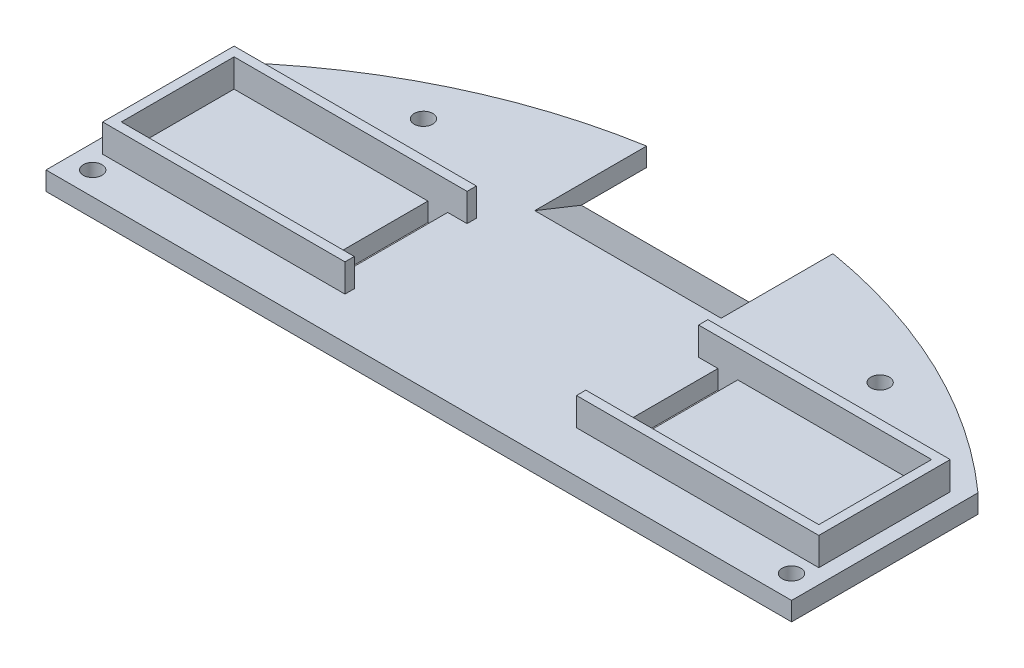
SolidWorks part; units mm, degrees
ref_plane "Front Plane" through (0, 0, 0) normal (0, 0, 1) x (1, 0, 0)
ref_plane "Top Plane" through (0, 0, 0) normal (0, 1, 0) x (1, 0, 0)
ref_plane "Right Plane" through (0, 0, 0) normal (1, 0, 0) x (0, 0, -1)
sketch "Sketch2" plane through (0, 0, 0) normal (0, 1, 0) x (1, 0, 0)
  line L0 (-10, 24.4394) -> (-10, 17.4394)
  line L1 (-40, -10) -> (40, -10)
  line L2 (-40, -10) -> (-40, 10)
  line L4 (40, -10) -> (40, 10)
  line L5 (-40, -10) -> (40, 10) construction
  line L6 (-40, 10) -> (40, -10) construction
  line L7 (0, -55) -> (0, 55) construction
  line L8 (-10, 17.4394) -> (10, 17.4394)
  line L13 (14.5, 7.6) -> (16.62, 7.6)
  line L14 (14.5, 7.6) -> (14.5, -4.5)
  line L15 (14.5, -4.5) -> (16.62, -4.5)
  line L16 (16.62, 7.6) -> (16.62, -4.5)
  line L21 (10, 17.4394) -> (10, 24.4394)
  line L22 (0, 17.4394) -> (0, -10) construction
  line L23 (-14.5, -4.5) -> (-16.62, -4.5)
  line L24 (-16.62, 7.6) -> (-16.62, -4.5)
  line L25 (-14.5, 7.6) -> (-16.62, 7.6)
  line L26 (-14.5, 7.6) -> (-14.5, -4.5)
  arc A0 (-40, 10) -> (-10, 24.4394) centre (0, -34.7214) cw
  arc A1 (10, 24.4394) -> (40, 10) centre (0, -34.7214) cw
  circle A3 centre (-37.4904, -7.5) radius 1
  circle A6 centre (37.4904, -7.5) radius 1
  circle A8 centre (-24.5, 15) radius 1
  circle A9 centre (24.5, 15) radius 1
  point P0 (0, 0)
  point P9 (0, -10)
  point P30 (0, 17.4394)
  dimension "D3" = 60
  dimension "D4" = 2
  dimension "D7" = 2
  dimension "D1" = 80
  dimension "D2" = 20
  dimension "D5" = 37.4904
  dimension "D6" = 7.5
  dimension "D8" = 15
  dimension "D9" = 24.5
  dimension "D10" = 20
  dimension "D11" = 7
  dimension "D12" = 2.12
  dimension "D13" = 12.1
  dimension "D14" = 3
  dimension "D15" = 14.5
extrude "Boss-Extrude2" add sketch "Sketch2" along normal blind 2
sketch "Sketch3" plane through (0, 2, 0) normal (0, 1, 0) x (1, 0, 0)
  line L0 (16.62, -4.5) -> (16.62, 7.6) construction
  line L1 (12.42, -4.5) -> (37.42, -4.5)
  line L2 (12.42, -4.5) -> (12.42, -5.5)
  line L3 (12.42, -5.5) -> (38.42, -5.5)
  line L6 (38.42, -5.5) -> (38.42, 8.6)
  line L8 (37.42, -4.5) -> (37.42, 7.6)
  line L9 (37.42, 7.6) -> (12.42, 7.6)
  line L11 (38.42, 8.6) -> (12.42, 8.6)
  line L12 (12.42, 7.6) -> (12.42, 8.6)
  line L13 (16.62, 7.6) -> (14.5, 7.6) construction
  line L14 (14.5, -4.5) -> (16.62, -4.5) construction
  line L15 (0, 0) -> (0, 17.4394) construction
  line L17 (10, 17.4394) -> (-10, 17.4394) construction
  line L18 (-12.42, -4.5) -> (-12.42, -5.5)
  line L19 (-12.42, -4.5) -> (-37.42, -4.5)
  line L20 (-37.42, -4.5) -> (-37.42, 7.6)
  line L21 (-37.42, 7.6) -> (-12.42, 7.6)
  line L22 (-12.42, 7.6) -> (-12.42, 8.6)
  line L23 (-38.42, 8.6) -> (-12.42, 8.6)
  line L24 (-38.42, -5.5) -> (-38.42, 8.6)
  line L25 (-12.42, -5.5) -> (-38.42, -5.5)
  point P10 (0, 17.4394)
  point P27 (0, 0)
  point P28 (12.3305, -5.5)
  dimension "D1" = 1
  dimension "D2" = 1
  dimension "D3" = 20.8
  dimension "D4" = 26
extrude "Boss-Extrude3" add sketch "Sketch3" along normal blind 3
chamfer "Chamfer1" distance 2 distance2 5 1 edges at (0, 2, -17.4394) first distance on face at (0, 1, -17.4394)
